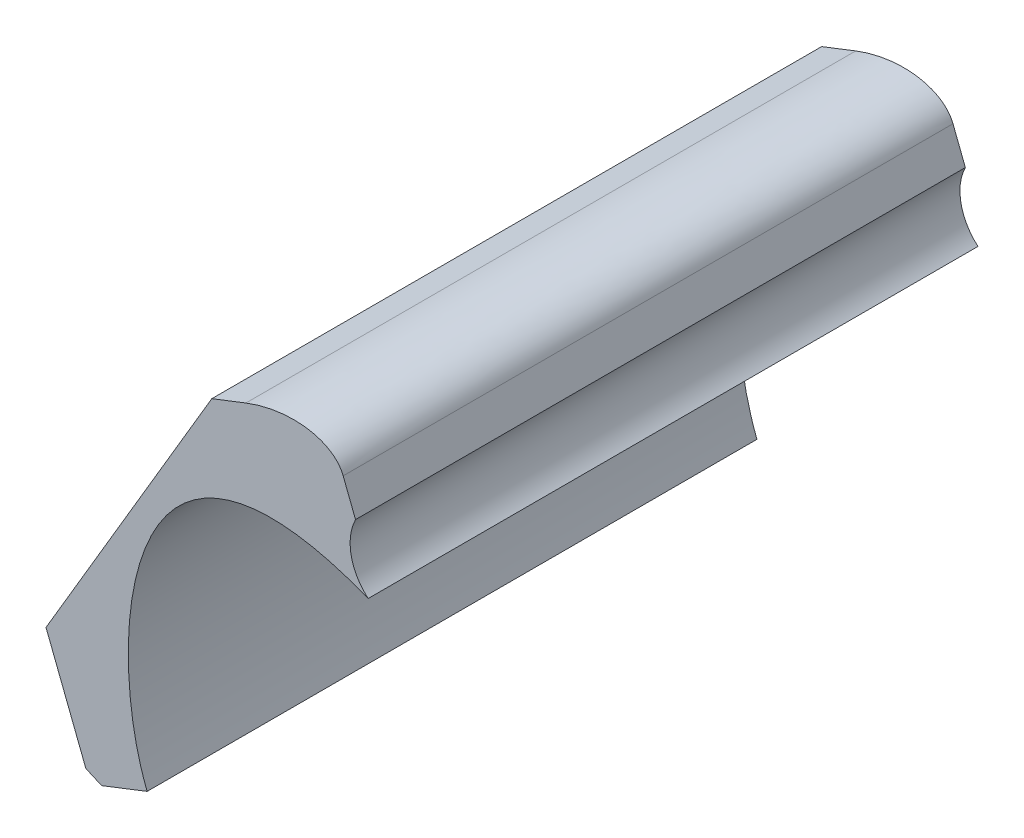
SolidWorks part; units mm, degrees
ref_plane "前基準面" through (0, 0, 0) normal (0, 0, 1) x (1, 0, 0)
ref_plane "上基準面" through (0, 0, 0) normal (0, 1, 0) x (1, 0, 0)
ref_plane "右基準面" through (0, 0, 0) normal (1, 0, 0) x (0, 0, -1)
sketch "草圖1" plane through (0, 0, 0) normal (0, 0, 1) x (1, 0, 0)
  line L0 (-103.6874, -122.2555) -> (-126.9808, -131.3338)
  line L1 (-126.9808, -131.3338) -> (-145.1374, -84.747)
  line L2 (-145.1374, -84.747) -> (-77.1642, 30.445)
  line L3 (-30.5774, 48.6016) -> (-18.2472, 16.9645)
  line L4 (-77.1642, 30.445) -> (-30.5774, 48.6016)
  arc A0 (-18.2472, 16.9645) -> (-13.0619, -8.4502) centre (0.5288, 7.559) ccw
  spline S0 degree 3 poles (-13.0619, -8.4502) (-61.976, 10.8916) (-107.3507, -14.3037) (-113.854, -82.4353) (-107.4293, -112.6837) (-103.6393, -122.3785) (-103.6152, -122.4403) knots 0.018552 0.018552 0.018552 0.018552 0.510085 0.835217 0.998955 1 1 1 1
  point P0 (0, 0)
  dimension "D1" = 25
  dimension "D2" = 50
  dimension "D3" = 50
extrude "填料-伸長1" add sketch "草圖1" against normal blind 250 contours S0 L3 L4 L2 L1 L0 region at (-116.1446, -124.715, 0)
fillet "圓角1" radius 35 1 edges at (-30.5774, 48.6016, -125) second distance 20 first distance on face at (-53.8708, 39.5233, -125)
chamfer "導角1" distance 5 angle 45 1 edges at (-126.9808, -131.3338, -125)
equation "\"ㄉ200\"=10"
